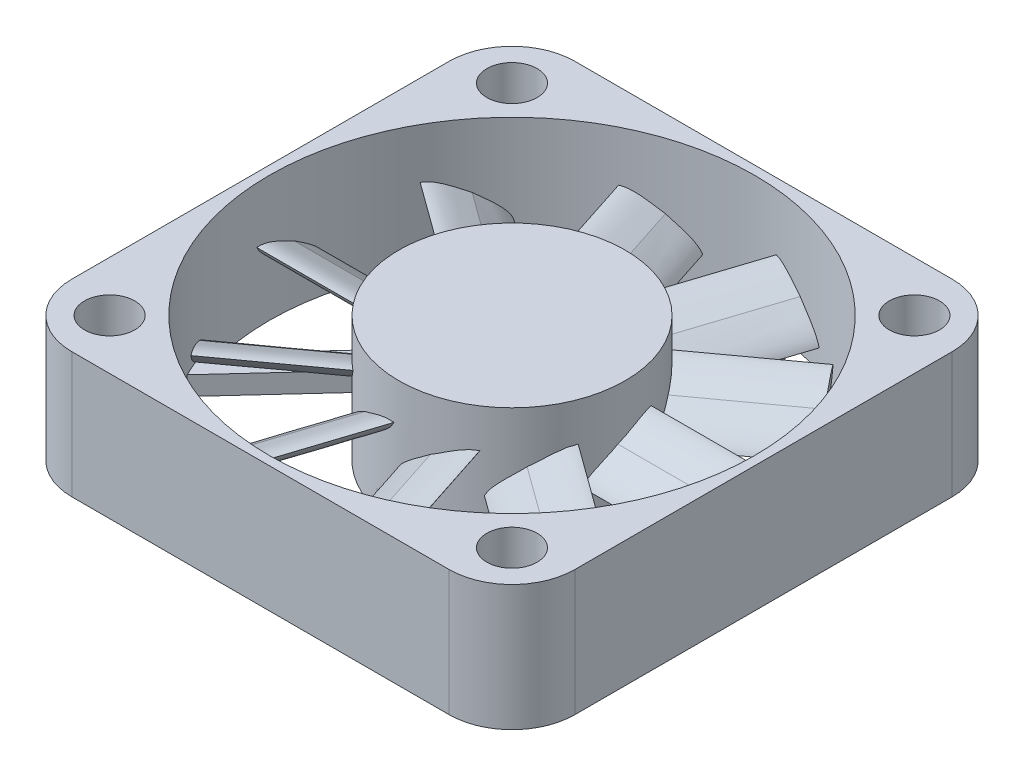
SolidWorks part; units mm, degrees
ref_plane "Front Plane" through (0, 0, 0) normal (0, 0, 1) x (1, 0, 0)
ref_plane "Top Plane" through (0, 0, 0) normal (0, 1, 0) x (1, 0, 0)
ref_plane "Right Plane" through (0, 0, 0) normal (1, 0, 0) x (0, 0, -1)
sketch "Sketch1" plane through (0, 0, 0) normal (0, 1, 0) x (1, 0, 0)
  line L1 (0, 0) -> (40, 0)
  line L2 (0, 0) -> (0, 40)
  line L3 (0, 40) -> (40, 40)
  line L4 (40, 0) -> (40, 40)
  dimension "D1" = 40
  dimension "D2" = 40
extrude "Boss-Extrude1" add sketch "Sketch1" along normal blind 10
sketch "Sketch2" plane through (0, 10, 0) normal (0, 1, 0) x (1, 0, 0)
  line L0 (20, 40) -> (20, 0) construction
  line L1 (40, 40) -> (0, 40) construction
  line L2 (0, 0) -> (40, 0) construction
  line L3 (0, 20) -> (40, 20) construction
  line L4 (0, 40) -> (0, 0) construction
  line L5 (40, 0) -> (40, 40) construction
  circle A0 centre (20, 20) radius 19.3
  dimension "D1" = 38.6
extrude "Cut-Extrude1" cut sketch "Sketch2" against normal blind 10
sketch "Sketch3" plane through (0, 0, 0) normal (0, -1, 0) x (1, 0, 0)
  line L0 (20, 0) -> (20, -40) construction
  line L1 (0, 0) -> (40, 0) construction
  line L2 (40, -40) -> (0, -40) construction
  line L3 (0, -20) -> (40, -20) construction
  line L4 (0, -40) -> (0, 0) construction
  line L5 (40, 0) -> (40, -40) construction
  line L6 (18.0374, -11.2166) -> (34.6996, -7.4936)
  line L7 (23.9943, -11.9349) -> (36.0265, -9.2464)
  line L8 (28.5879, -22.6921) -> (23.4811, -38.9835)
  line L9 (24.9874, -27.4917) -> (21.2996, -39.2562)
  line L10 (13.3746, -26.0913) -> (1.8193, -13.523)
  line L11 (11.0183, -20.5734) -> (2.6738, -11.4974)
  circle A0 centre (20, -20) radius 9
  circle A1 centre (20, -20) radius 19.3 construction
  circle A2 centre (20, -20) radius 19.3
  circle M8 centre (20, -20) radius 19.3
  dimension "D1" = 18
  dimension "D2" = 2
  dimension "D3" = 3
extrude "Boss-Extrude2" add sketch "Sketch3" against normal blind 1.5 contours A0 | A0 L7 L6 M8 | A0 L11 L10 M8 | A0 L9 L8 M8 region at (28.6371, 0, -9.8287) region at (20, 0, -20) region at (6.8729, 0, -17.6057) region at (24.49, 0, -32.5656)
sketch "Sketch4" plane through (0, 1.5, 0) normal (0, 1, 0) x (1, 0, 0)
  circle A0 centre (20, 20) radius 9
extrude "Boss-Extrude3" add sketch "Sketch4" along normal blind 8.5
sketch "Sketch5" plane through (0, 10, 0) normal (0, 1, 0) x (1, 0, 0)
  line L0 (20, 20) -> (29, 20) construction
  circle A0 centre (20, 20) radius 9 construction
ref_plane "Plane1" through (29, 10, -20) normal (1, 0, 0) x (0, 0, -1)
sketch "Sketch6" plane through (29, 10, -20) normal (1, 0, 0) x (0, 0, -1)
  line L4 (-0.5641, -4.0909) -> (0.0369, -5.1317) construction
  line L5 (2.3942, -3.0768) -> (-2.9214, -6.1458) construction
  spline S0 degree 3 poles (-0.5641, -4.0909) (-0.0422, -3.8393) (0.8773, -3.3386) (1.9153, -3.0339) (2.3942, -3.0768) knots 0 0 0 0 0.548109 1 1 1 1
  spline S1 degree 3 poles (0.0369, -5.1317) (0.5156, -4.8055) (1.4091, -4.2596) (2.1919, -3.513) (2.3942, -3.0768) knots 0 0 0 0 0.548109 1 1 1 1
  spline S2 degree 3 poles (0.0369, -5.1317) (-0.485, -5.3832) (-1.4045, -5.884) (-2.4425, -6.1886) (-2.9214, -6.1458) knots 0 0 0 0 0.548109 1 1 1 1
  spline S3 degree 3 poles (-0.5641, -4.0909) (-1.0428, -4.417) (-1.9363, -4.963) (-2.7191, -5.7096) (-2.9214, -6.1458) knots 0 0 0 0 0.548109 1 1 1 1
extrude "Boss-Extrude4" add sketch "Sketch6" along normal blind 9.9 from offset 1 separate body offset against normal yes
ref_plane "Plane2" through (0, 0, -20) normal (0, 0, 1) x (1, 0, 0)
sketch "Sketch7" plane through (0, 0, -20) normal (0, 0, 1) x (1, 0, 0)
  line L0 (20, 10) -> (20, 2.1954) construction
pattern_circular "CirPattern2" count 10 over 360 about axis through (20, 10, -20) along (0, -1, 0) of bodies 105
fillet "Fillet1" radius 5 4 edges at (0, 5, 0) (0, 5, -40) (40, 5, -40) (40, 5, 0)
sketch "Sketch8" plane through (0, 10, 0) normal (0, 1, 0) x (1, 0, 0)
  line L0 (20, 40) -> (20, -3.7843) construction
  line L1 (35, 40) -> (5, 40) construction
  line L2 (20, 20) -> (58.8713, 20) construction
  line L3 (-5.5, 20) -> (5.5, 20) construction
  circle A0 centre (36, 36) radius 2
  circle A1 centre (4, 36) radius 2
  circle A2 centre (36, 4) radius 2
  circle A3 centre (4, 4) radius 2
  dimension "D3" = 4
  dimension "D1" = 32
  dimension "D2" = 16
  dimension "D4" = 16
extrude "Cut-Extrude2" cut sketch "Sketch8" against normal blind 10
